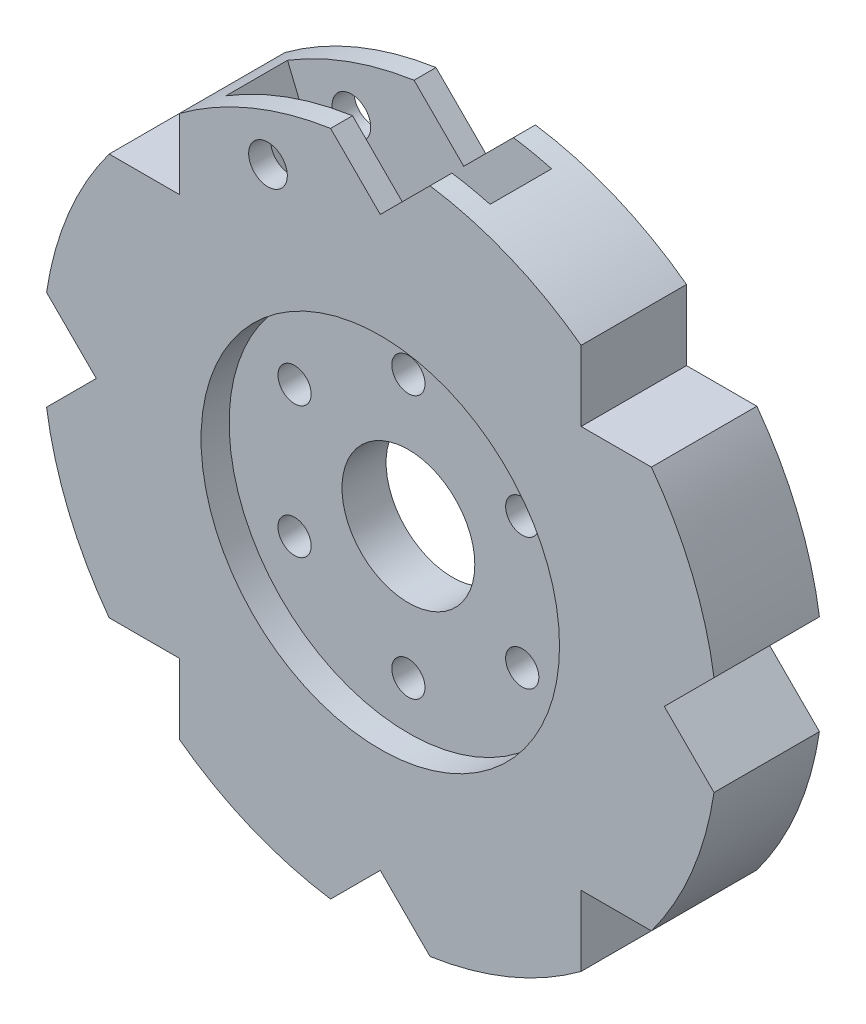
SolidWorks part; units mm, degrees
material "PE High Density Film"
ref_plane "Front Plane" through (0, 0, 0) normal (0, 0, 1) x (1, 0, 0)
ref_plane "Top Plane" through (0, 0, 0) normal (0, 1, 0) x (1, 0, 0)
ref_plane "Right Plane" through (0, 0, 0) normal (1, 0, 0) x (0, 0, -1)
sketch "Sketch1" plane through (0, 0, 0) normal (0, 0, 1) x (1, 0, 0)
  line L0 (0, 0) -> (0, 60.96) construction
  line L1 (-8.9803, 60.2949) -> (0, 51.3147)
  line L2 (0, 51.3147) -> (8.9803, 60.2949)
  line L3 (36.2849, 48.9849) -> (36.2849, 36.2849)
  line L4 (36.2849, 36.2849) -> (48.9849, 36.2849)
  line L5 (60.2949, 8.9803) -> (51.3147, 0)
  line L6 (51.3147, 0) -> (60.2949, -8.9803)
  line L7 (48.9849, -36.2849) -> (36.2849, -36.2849)
  line L8 (36.2849, -36.2849) -> (36.2849, -48.9849)
  line L9 (8.9803, -60.2949) -> (0, -51.3147)
  line L10 (0, -51.3147) -> (-8.9803, -60.2949)
  line L11 (-36.2849, -48.9849) -> (-36.2849, -36.2849)
  line L12 (-36.2849, -36.2849) -> (-48.9849, -36.2849)
  line L13 (-60.2949, -8.9803) -> (-51.3147, 0)
  line L14 (-51.3147, 0) -> (-60.2949, 8.9803)
  line L15 (-48.9849, 36.2849) -> (-36.2849, 36.2849)
  line L16 (-36.2849, 36.2849) -> (-36.2849, 48.9849)
  arc A0 (-60.2949, -8.9803) -> (-48.9849, -36.2849) centre (0, 0) ccw
  arc A1 (-48.9849, 36.2849) -> (-60.2949, 8.9803) centre (0, 0) ccw
  arc A2 (-36.2849, -48.9849) -> (-8.9803, -60.2949) centre (0, 0) ccw
  arc A3 (8.9803, -60.2949) -> (36.2849, -48.9849) centre (0, 0) ccw
  arc A4 (48.9849, -36.2849) -> (60.2949, -8.9803) centre (0, 0) ccw
  arc A5 (60.2949, 8.9803) -> (48.9849, 36.2849) centre (0, 0) ccw
  arc A6 (36.2849, 48.9849) -> (8.9803, 60.2949) centre (0, 0) ccw
  arc A7 (-8.9803, 60.2949) -> (-36.2849, 48.9849) centre (0, 0) ccw
  point P30 (0, 0)
  dimension "D1" = 121.92
  dimension "D2" = 45
  dimension "D3" = 12.7
  dimension "D4" = 8
extrude "Boss-Extrude1" add sketch "Sketch1" along normal blind 19.05
sketch "Sketch2" plane through (0, 0, 19.05) normal (0, 0, 1) x (1, 0, 0)
  circle A0 centre (0, 0) radius 12
  dimension "D1" = 24
extrude "Cut-Extrude1" cut sketch "Sketch2" against normal through all contours A0 region at (0, 0, 19.05)
sketch "Sketch3" plane through (0, 0, 19.05) normal (0, 0, 1) x (1, 0, 0)
  circle A0 centre (0, 0) radius 32.385
  dimension "D1" = 64.77
extrude "Cut-Extrude2" cut sketch "Sketch3" against normal blind 5.08
sketch "Sketch4" plane through (0, 0, 0) normal (0, 0, -1) x (-1, 0, 0)
  circle A0 centre (0, 0) radius 28.4
  dimension "D1" = 56.8
extrude "Cut-Extrude3" cut sketch "Sketch4" against normal blind 6
sketch "Sketch5" plane through (0, 0, 6) normal (0, 0, -1) x (-1, 0, 0)
  line L0 (0, 0) -> (0, 23.75) construction
  circle A0 centre (0, 0) radius 23.75 construction
  circle A1 centre (0, 23.75) radius 2.6
  circle A2 centre (20.5681, 11.875) radius 2.6
  circle A3 centre (20.5681, -11.875) radius 2.6
  circle A4 centre (0, -23.75) radius 2.6
  circle A5 centre (-20.5681, -11.875) radius 2.6
  circle A6 centre (-20.5681, 11.875) radius 2.6
  point P17 (0, 0)
  dimension "D1" = 47.5
  dimension "D2" = 5.2
  dimension "D3" = 6
hole_wizard "Ø6.0mm Dowel Hole1" positions "Sketch6" profile "Sketch8" hole size "Ø6.0" standard "ANSI Metric" end condition through all
sketch "Sketch6" plane through (0, 0, 6) normal (0, 0, -1) x (-1, 0, 0)
  point P0 (0, 23.75)
  point P3 (20.5681, 11.875)
  point P6 (20.5681, -11.875)
  point P9 (0, -23.75)
  point P13 (-20.5681, 11.875)
  point P16 (-20.5681, -11.875)
sketch "Sketch8" plane through (0, 23.75, 6) normal (1, 0, 0) x (0, 1, 0)
  line L0 (0, 0) -> (0, 13.05)
  line L1 (0, 13.05) -> (3, 13.05)
  line L2 (3, 13.05) -> (3, 0)
  line L5 (3, 0) -> (0, 0)
  line L11 (0, -6.35) -> (0, 107.95) construction
  dimension "Thru Hole Dia." = 6
  dimension "Thru Hole Depth" = 13.05
ref_plane "Plane1" through (0, 0, 9.525) normal (0, 0, -1) x (-1, 0, 0)
sketch "Sketch9" plane through (0, 0, 9.525) normal (0, 0, -1) x (-1, 0, 0)
  line L0 (0, 0) -> (23.3284, 56.3197) construction
  line L1 (20.2908, 48.9864) -> (11.4909, 52.6315) construction
  line L2 (17.2533, 41.6531) -> (8.4533, 45.2982)
  line L3 (8.4533, 45.2982) -> (14.5284, 59.9648)
  line L4 (14.5284, 59.9648) -> (32.1283, 52.6746)
  line L5 (32.1283, 52.6746) -> (26.0532, 38.008)
  line L6 (26.0532, 38.008) -> (17.2533, 41.6531)
  arc A0 (36.2849, 48.9849) -> (8.9803, 60.2949) centre (0, 0) ccw construction
  circle A1 centre (20.2908, 48.9864) radius 3.4925
  point P11 (0, 0)
  dimension "D1" = 6.985
  dimension "D2" = 7.9375
  dimension "D3" = 19.05
extrude "Cut-Extrude4" cut sketch "Sketch9" against normal mid plane 11.1125
sketch "Sketch10" plane through (0, 0, 0) normal (0, 0, -1) x (-1, 0, 0)
  circle A0 centre (20.2908, 48.9864) radius 3.4925
  circle A1 centre (20.2908, 48.9864) radius 3.4925 construction
extrude "Cut-Extrude5" cut sketch "Sketch10" against normal through all
sketch "Sketch11" plane through (0, 0, 9.525) normal (0, 0, -1) x (-1, 0, 0)
  line L0 (0, 0) -> (0, 50.8) construction
  line L1 (0, 38.1) -> (-15.875, 38.1)
  line L2 (-15.875, 38.1) -> (-15.875, 63.5)
  line L3 (-15.875, 63.5) -> (15.875, 63.5)
  line L4 (15.875, 63.5) -> (15.875, 38.1)
  line L5 (15.875, 38.1) -> (0, 38.1)
  line L6 (0, 50.8) -> (-15.875, 50.8) construction
  line L7 (0, 0) -> (25.4, 0) construction
  dimension "D1" = 25.4
  dimension "D2" = 90
  dimension "D3" = 31.75
  dimension "D4" = 25.4
  dimension "D5" = 50.8
extrude "Cut-Extrude6" cut sketch "Sketch11" against normal mid plane 11.1125
equation "\"D2@Sketch9\"=0.3125"
